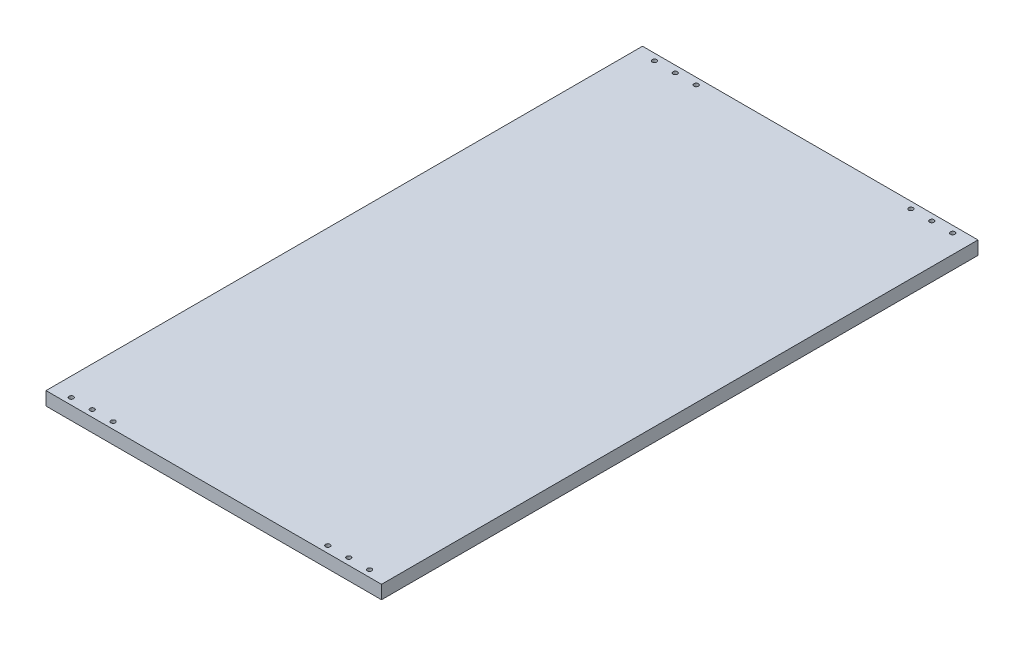
SolidWorks part; units mm, degrees
ref_plane "Спереди" through (0, 0, 0) normal (0, 0, 1) x (1, 0, 0)
ref_plane "Сверху" through (0, 0, 0) normal (0, 1, 0) x (1, 0, 0)
ref_plane "Справа" through (0, 0, 0) normal (1, 0, 0) x (0, 0, -1)
sketch "Эскиз1" plane through (0, 0, 0) normal (0, 1, 0) x (1, 0, 0)
  line L1 (0, 0) -> (450, 0)
  line L2 (0, 0) -> (0, 800)
  line L3 (0, 800) -> (450, 800)
  line L4 (450, 0) -> (450, 800)
extrude "Бобышка-Вытянуть1" add sketch "Эскиз1" along normal blind 18
sketch "Эскиз2" plane through (0, 18, 0) normal (0, 1, 0) x (1, 0, 0)
  line L0 (0, 400) -> (472.9857, 400) construction
  line L1 (0, 800) -> (0, 0) construction
  line L2 (225, 800) -> (225, -34.8514) construction
  line L3 (450, 800) -> (0, 800) construction
  circle A0 centre (25, 9) radius 3
  circle A1 centre (53, 9) radius 3
  circle A2 centre (81, 9) radius 3
  circle A12 centre (369, 9) radius 3
  circle A13 centre (397, 9) radius 3
  circle A14 centre (425, 9) radius 3
  circle A15 centre (425, 791) radius 3
  circle A16 centre (397, 791) radius 3
  circle A17 centre (369, 791) radius 3
  circle A18 centre (81, 791) radius 3
  circle A19 centre (53, 791) radius 3
  circle A20 centre (25, 791) radius 3
  dimension "D1" = 3
extrude "Вырез-Вытянуть1" cut sketch "Эскиз2" against normal blind 9
